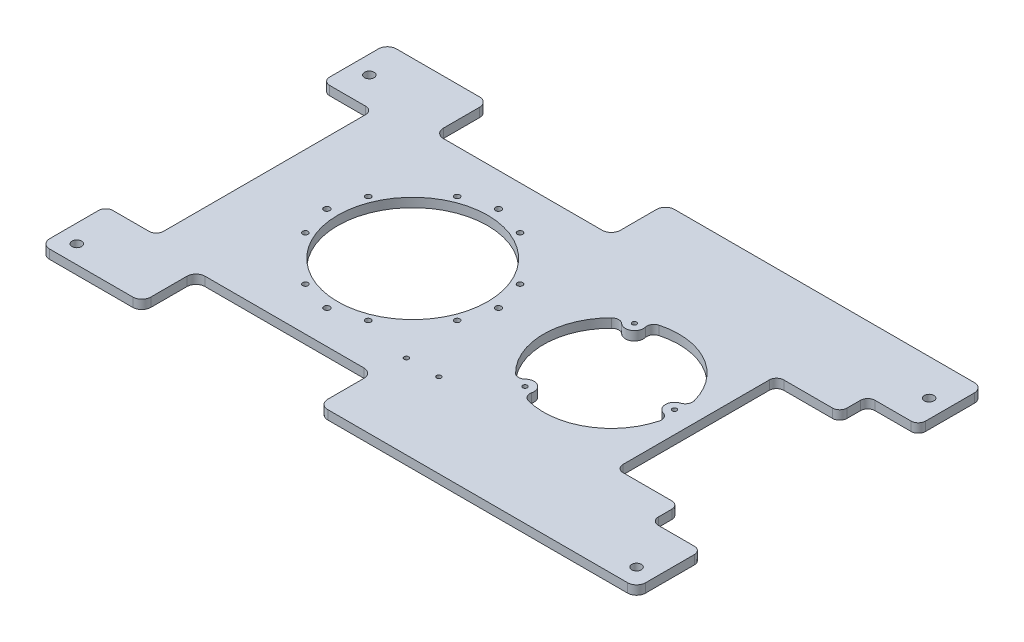
SolidWorks part; units mm, degrees
material "6061 Alloy"
ref_plane "Front Plane" through (0, 0, 0) normal (0, 0, 1) x (1, 0, 0)
ref_plane "Top Plane" through (0, 0, 0) normal (0, 1, 0) x (1, 0, 0)
ref_plane "Right Plane" through (0, 0, 0) normal (1, 0, 0) x (0, 0, -1)
sketch "Sketch1" plane through (0, 0, 0) normal (0, 1, 0) x (1, 0, 0)
  line L1 (0, 0) -> (330, 0)
  line L2 (0, 0) -> (0, 192)
  line L3 (0, 192) -> (330, 192)
  line L4 (330, 0) -> (330, 192)
  dimension "D1" = 192
  dimension "D2" = 330
extrude "Boss-Extrude1" add sketch "Sketch1" along normal blind 5
sketch "Sketch2" plane through (0, 5, 0) normal (0, 1, 0) x (1, 0, 0)
  line L0 (0, 0) -> (330, 0) construction
  line L1 (0, 0) -> (0, 192)
  line L2 (135.5, 96) -> (110, 96) construction
  line L3 (110, 96) -> (0, 96) construction
  line L4 (152.0365, 113.4121) -> (110, 96) construction
  circle A0 centre (110, 96) radius 50 construction
  circle A1 centre (110, 96) radius 45.5 construction
  circle A10 centre (152.0365, 113.4121) radius 1.5
  circle A11 centre (152.0365, 78.5879) radius 1.5
  circle A12 centre (127.4121, 53.9635) radius 1.5
  circle A13 centre (92.5879, 53.9635) radius 1.5
  circle A14 centre (67.9635, 78.5879) radius 1.5
  circle A15 centre (67.9635, 113.4121) radius 1.5
  circle A16 centre (92.5879, 138.0365) radius 1.5
  circle A17 centre (127.4121, 138.0365) radius 1.5
  point P8 (0, 0)
  point P9 (0, 0)
  point P21 (110, 96)
  point P30 (110, 96)
  dimension "D1" = 100
  dimension "D2" = 91
  dimension "D3" = 22.5
  dimension "D8" = 8
  dimension "D4" = 3
  dimension "D5" = 192
  dimension "D6" = 330
  dimension "D7" = 110
extrude "Cut-Extrude1" cut sketch "Sketch2" against normal through all and the other way through all contours A16 | A17 | A10 | A11 | A12 | A13 | A14 | A15
sketch "Sketch3" plane through (0, 5, 0) normal (0, 1, 0) x (1, 0, 0)
  line L0 (0, 0) -> (0, 192)
  line L1 (0, 0) -> (330, 0)
  line L2 (0, 0) -> (330, 0) construction
  circle A0 centre (110, 96) radius 41.5
  circle A1 centre (110, 96) radius 44 construction
  circle A5 centre (67.9635, 113.4121) radius 1.5 construction
  circle A6 centre (92.5879, 53.9635) radius 1.5 construction
  circle A7 centre (152.0365, 113.4121) radius 1.5 construction
  dimension "D1" = 83
  dimension "D2" = 330
  dimension "D3" = 192
extrude "Cut-Extrude2" cut sketch "Sketch3" against normal through all contours A0 region at (110, 5, -96)
hole_wizard "M5 Clearance Hole1" positions "Sketch13" profile "Sketch14" hole size "M5" standard "DIN"
sketch "Sketch13" plane through (0, 5, 0) normal (0, 1, 0) x (1, 0, 0)
  line L0 (0, 192) -> (0, 0) construction
  line L1 (330, 0) -> (330, 192) construction
  line L2 (10, 172) -> (320, 172) construction
  line L3 (320, 172) -> (320, 10) construction
  line L4 (320, 10) -> (10, 10) construction
  line L5 (10, 10) -> (10, 172) construction
  line L15 (330, 192) -> (0, 192) construction
  point P0 (10, 172)
  point P2 (10, 10)
  point P4 (320, 10)
  point P6 (320, 172)
  dimension "D1" = 10
  dimension "D2" = 10
  dimension "D3" = 10
  dimension "D4" = 10
  dimension "D5" = 162
  dimension "D6" = 162
  dimension "D7" = 20
sketch "Sketch14" plane through (10, 5, -172) normal (1, 0, 0) x (0, 0, 1)
  line L0 (0, 0) -> (0, 13.5323)
  line L1 (0, 13.5323) -> (2.65, 11.94)
  line L2 (2.65, 11.94) -> (2.65, 0)
  line L5 (2.65, 0) -> (0, 0)
  line L10 (0, 13.5323) -> (-2.65, 11.94) construction
  line L11 (0, -6.35) -> (0, 107.95) construction
  dimension "Hole Dia." = 5.3
  dimension "Hole Depth" = 11.94
  dimension "Drill Angle" = 118
hole_wizard "Tap Drill for M4 Tap1" positions "Sketch17" profile "Sketch18" hole size "M4" standard "DIN" end condition through all
sketch "Sketch17" plane through (0, 5, 0) normal (0, 1, 0) x (1, 0, 0)
  line L0 (152.0365, 113.4121) -> (152.0365, 78.5879)
  line L2 (152.0365, 96) -> (157.5, 96)
  line L3 (62.5, 96) -> (157.5, 96) construction
  circle A0 centre (110, 96) radius 47.5
  circle A1 centre (110, 96) radius 41.5 construction
  circle A3 centre (110, 96) radius 47.5 construction
  circle A6 centre (152.0365, 78.5879) radius 1.5 construction
  circle A7 centre (152.0365, 113.4121) radius 1.5 construction
  point P0 (157.5, 96)
  point P22 (110, 48.5)
  point P23 (62.5, 96)
  point P24 (110, 143.5)
  dimension "D1" = 95
  dimension "D2" = 4
sketch "Sketch18" plane through (157.5, 5, -96) normal (1, 0, 0) x (0, 0, 1)
  line L0 (0, 0) -> (0, 5)
  line L1 (0, 5) -> (1.65, 5)
  line L2 (1.65, 5) -> (1.65, 0)
  line L5 (1.65, 0) -> (0, 0)
  line L11 (0, -6.35) -> (0, 107.95) construction
  dimension "Thru Hole Dia." = 3.3
  dimension "Thru Hole Depth" = 5
sketch "Sketch19" plane through (0, 5, 0) normal (0, 1, 0) x (1, 0, 0)
  line L0 (0, 192) -> (0, 0) construction
  line L1 (0, 156) -> (28, 156)
  line L2 (0, 156) -> (0, 36)
  line L3 (0, 36) -> (28, 36)
  line L4 (28, 156) -> (28, 36)
  line L5 (330, 0) -> (330, 192) construction
  line L6 (330, 156) -> (302, 156)
  line L7 (330, 156) -> (330, 36)
  line L8 (330, 36) -> (302, 36)
  line L9 (302, 156) -> (302, 36)
  line L10 (0, 96) -> (28, 96) construction
  dimension "D1" = 120
  dimension "D2" = 28
extrude "Cut-Extrude3" cut sketch "Sketch19" against normal through all and the other way through all
sketch "Sketch21" plane through (0, 0, 0) normal (0, -1, 0) x (1, 0, 0)
  line L1 (302, -51.5) -> (267, -51.5)
  line L2 (302, -51.5) -> (302, -140.5)
  line L3 (302, -140.5) -> (267, -140.5)
  line L4 (267, -51.5) -> (267, -140.5)
  line L5 (302, -96) -> (302, -156) construction
  line L6 (302, -96) -> (302, -36) construction
  circle A0 centre (190.7932, -95.584) radius 40 construction
  dimension "D3" = 80
  dimension "D1" = 35
  dimension "D2" = 89
extrude "Cut-Extrude4" cut sketch "Sketch21" against normal through all
fillet "Fillet1" radius 4 12 edges at (330, 2.5, -36) (302, 2.5, -36) (330, 2.5, -156) (302, 2.5, -156) (28, 2.5, -156) (28, 2.5, -36) (0, 2.5, -36) (0, 2.5, -156) (267, 2.5, -51.5) (267, 2.5, -140.5) (302, 2.5, -140.5) (302, 2.5, -51.5)
sketch "Sketch23" plane through (0, 0, 0) normal (0, 0, 1) x (1, 0, 0)
  line L0 (151.5, 5) -> (68.5, 5) construction
  line L1 (151.5, 5) -> (68.5, 5)
  point P2 (165, 3)
  point P3 (110, 5)
ref_axis "Axis1" through (110, 5, 0) along (0, 0, -1)
sketch "Sketch24" plane through (267, 0, 0) normal (1, 0, 0) x (0, 0, -1)
  line L0 (137.5, 5) -> (54.5, 5) construction
  line L1 (137.5, 5) -> (54.5, 5)
  point P2 (96, 3)
ref_axis "Axis2" through (267, 3, -96) along (-1, 0, 0)
hole_wizard "Tap Drill for M3 Tap1" positions "Sketch25" profile "Sketch26" hole size "M3" standard "DIN" end condition up to next
sketch "Sketch25" plane through (0, 0, 0) normal (0, -1, 0) x (-1, 0, 0)
  line L0 (-267, 96) -> (-230.0032, 96) construction
  line L1 (-202.5, 126.3109) -> (-202.5, 65.6891) construction
  circle A0 centre (-220, 96) radius 35 construction
  circle A1 centre (-110, 96) radius 41.5 construction
  point P6 (-202.5, 65.6891)
  point P14 (-255, 96)
  point P15 (-202.5, 126.3109)
  dimension "D1" = 70
  dimension "D3" = 110
  dimension "D2" = 3
sketch "Sketch26" plane through (202.5, 0, -126.3109) normal (1, 0, 0) x (0, 0, -1)
  line L0 (0, 0) -> (0, 5)
  line L1 (0, 5) -> (1.25, 5)
  line L2 (1.25, 5) -> (1.25, 0)
  line L5 (1.25, 0) -> (0, 0)
  line L11 (0, -6.35) -> (0, 107.95) construction
  dimension "Thru Hole Dia." = 2.5
  dimension "Thru Hole Depth" = 5
sketch "Sketch29" plane through (0, 0, 0) normal (0, -1, 0) x (1, 0, 0)
  line L0 (200, -67.5) -> (90, -67.5)
  line L1 (145, -67.5) -> (145, -24.0733)
hole_wizard "Tap Drill for M3 Tap2" positions "Sketch30" profile "Sketch31" hole size "M3" standard "DIN" end condition up to next
sketch "Sketch30" plane through (0, 0, 0) normal (0, -1, 0) x (-1, 0, 0)
  point P0 (-174, 46.5)
  point P3 (-156, 46.5)
  dimension "D1" = 18
  dimension "D2" = 29
  dimension "D3" = 21
sketch "Sketch31" plane through (174, 0, -46.5) normal (1, 0, 0) x (0, 0, -1)
  line L0 (0, 0) -> (0, 5)
  line L1 (0, 5) -> (1.25, 5)
  line L2 (1.25, 5) -> (1.25, 0)
  line L5 (1.25, 0) -> (0, 0)
  line L11 (0, -6.35) -> (0, 107.95) construction
  dimension "Thru Hole Dia." = 2.5
  dimension "Thru Hole Depth" = 5
sketch "Sketch32" plane through (0, 0, 0) normal (0, -1, 0) x (1, 0, 0)
  circle A0 centre (220, -96) radius 35 construction
  circle A1 centre (220, -96) radius 37.5
  circle A2 centre (202.5, -65.6891) radius 5
  circle A3 centre (202.5, -126.3109) radius 5
  circle A4 centre (255, -96) radius 5
  point P0 (202.5, -65.6891)
  point P1 (202.5, -126.3109)
  point P2 (255, -96)
  dimension "D1" = 75
  dimension "D2" = 10
extrude "Cut-Extrude5" cut sketch "Sketch32" against normal through all contours A4 A1 A2 A3 region at (220, 0, -96)
fillet "Fillet2" radius 4 6 edges at (257.2321, 2.5, -91.5259) (257.2321, 2.5, -100.4741) (197.5092, 2.5, -126.0069) (205.2586, 2.5, -130.481) (205.2586, 2.5, -61.519) (197.5092, 2.5, -65.9931)
sketch "Sketch33" plane through (0, 0, 0) normal (0, -1, 0) x (1, 0, 0)
  line L0 (56, 0) -> (56, -40) construction
  line L1 (0, 0) -> (56, 0) construction
  line L2 (0, 0) -> (0, -40) construction
  line L3 (0, -40) -> (56, -40) construction
  line L4 (28, 0) -> (28, -40) construction
  line L5 (330, 0) -> (204, 0) construction
  line L6 (330, 0) -> (330, -55.5) construction
  line L7 (330, -55.5) -> (204, -55.5) construction
  line L8 (267, 0) -> (267, -55.5) construction
  line L9 (204, 0) -> (204, -55.5) construction
  line L11 (56, 0) -> (154, 0)
  line L12 (56, 0) -> (56, -30)
  line L13 (56, -30) -> (154, -30)
  line L14 (154, 0) -> (154, -30)
  line L15 (28, -96) -> (85.3759, -96) construction
  line L16 (28, -40) -> (28, -152) construction
  line L17 (56, -162) -> (154, -162)
  line L18 (154, -192) -> (154, -162)
  line L19 (56, -192) -> (154, -192)
  line L20 (56, -192) -> (56, -162)
  dimension "D1" = 30
extrude "Cut-Extrude6" cut sketch "Sketch33" against normal through all
fillet "Fillet3" radius 5 12 edges at (154, 2.5, -192) (154, 2.5, -162) (56, 2.5, -162) (56, 2.5, -192) (154, 2.5, 0) (154, 2.5, -30) (56, 2.5, 0) (56, 2.5, -30) (330, 2.5, -192) (330, 2.5, 0) (0, 2.5, 0) (0, 2.5, -192)
equation "\"D2@Sketch13\"=\"D1@Sketch13\""
equation "\"D3@Sketch13\"=\"D1@Sketch13\""
equation "\"D4@Sketch13\"=\"D1@Sketch13\""
equation "\"D6@Sketch13\"=\"D5@Sketch13\""
